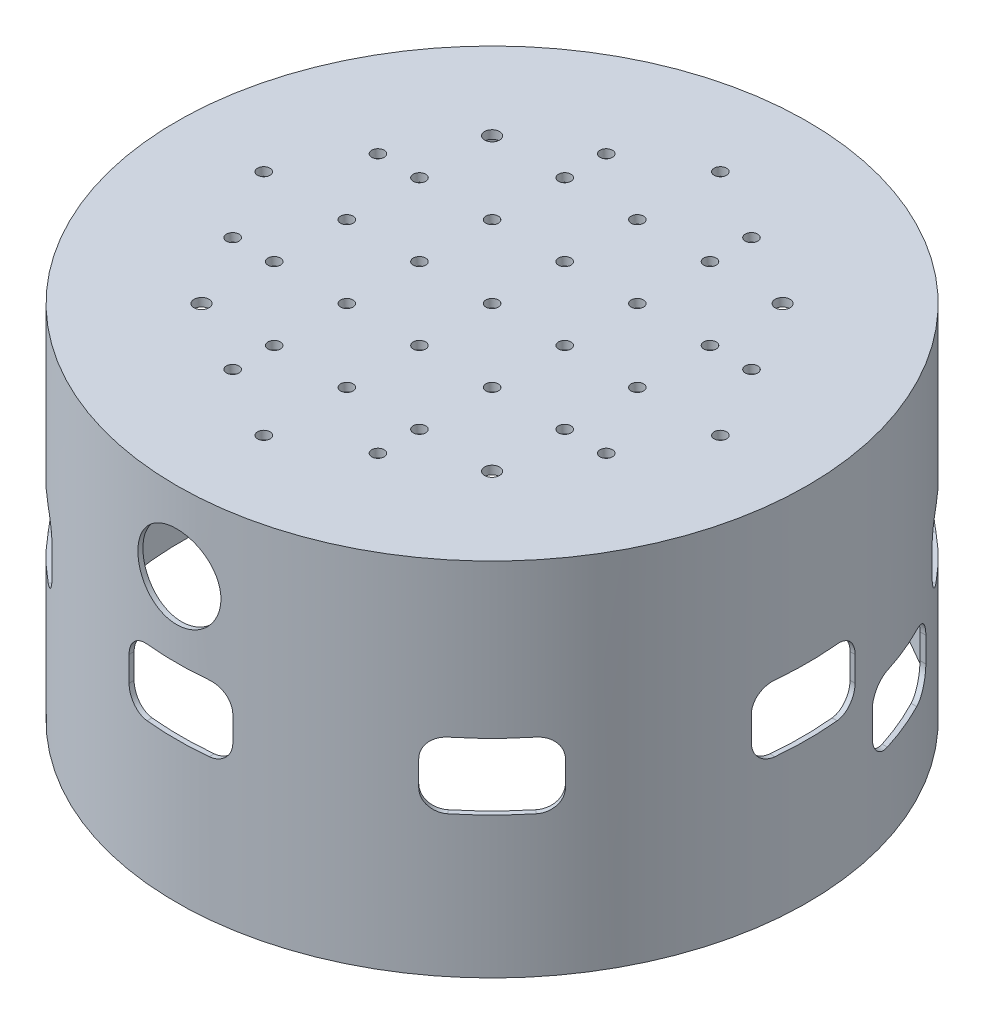
SolidWorks part; units mm, degrees
ref_plane "Front Plane" through (0, 0, 0) normal (0, 0, 1) x (1, 0, 0)
ref_plane "Top Plane" through (0, 0, 0) normal (0, 1, 0) x (1, 0, 0)
ref_plane "Right Plane" through (0, 0, 0) normal (1, 0, 0) x (0, 0, -1)
sketch "Sketch1" plane through (0, 0, 0) normal (0, 1, 0) x (1, 0, 0)
  circle A1 centre (0, 0) radius 76
extrude "Boss-Extrude1" add sketch "Sketch1" along normal blind 2
sketch "Sketch2" plane through (0, 0, 0) normal (0, -1, 0) x (1, 0, 0)
  circle A0 centre (0, 0) radius 76
  circle A1 centre (0, 0) radius 74
extrude "Boss-Extrude2" add sketch "Sketch2" along normal blind 85
ref_plane "Plane1" through (0, 0, 76) normal (0, 0, 1) x (1, 0, 0)
ref_plane "Plane2" through (-76, 0, 0) normal (-1, 0, 0) x (0, 0, 1)
sketch "Sketch4" plane through (0, 0, 76) normal (0, 0, 1) x (1, 0, 0)
  line L0 (0, 2) -> (0, -85) construction
  line L1 (76, 2) -> (-76, 2) construction
  line L2 (-76, -85) -> (76, -85) construction
  line L6 (0, 0) -> (0, -11) construction
  line L7 (83.6, 0) -> (-83.6, 0) construction
  line L8 (-10, -32) -> (10, -32) construction
  line L9 (-10, -32) -> (-10, -2) construction
  line L10 (-10, -2) -> (10, -2) construction
  line L11 (10, -32) -> (10, -2) construction
  line L12 (-10, -32) -> (10, -2) construction
  line L13 (-10, -2) -> (10, -32) construction
  circle A0 centre (0, -17) radius 10
  point P0 (0, -17)
  dimension "D1" = 2
  dimension "D3" = 30
  dimension "D2" = 20
extrude "Cut-Extrude1" cut sketch "Sketch4" against normal blind 10
sketch "Sketch5" plane through (0, 0, 76) normal (0, 0, 1) x (1, 0, 0)
  line L0 (0, -47.85) -> (0, 47.85) construction
  line L1 (-12.5, -51) -> (12.5, -51)
  line L2 (-12.5, -51) -> (-12.5, -35)
  line L3 (-12.5, -35) -> (12.5, -35)
  line L4 (12.5, -51) -> (12.5, -35)
  line L5 (-12.5, -51) -> (12.5, -35) construction
  line L6 (-12.5, -35) -> (12.5, -51) construction
  line L10 (0, -35) -> (0, 0) construction
  point P0 (0, -43)
  dimension "D1" = 35
extrude "Cut-Extrude2" cut sketch "Sketch5" against normal blind 10
fillet "Fillet1" radius 5 4 edges at (12.5, -51, 73.9508) (12.5, -35, 73.9508) (-12.5, -51, 73.9508) (-12.5, -35, 73.9508)
pattern_circular "CirPattern1" count 8 every 45 about axis through (0, 2, 0) along (0, 1, 0) of "Cut-Extrude2", "Fillet1"
sketch "Sketch6" plane through (0, 2, 0) normal (0, 1, 0) x (1, 0, 0)
  line L0 (-35, 0) -> (-75, 0) construction
  line L1 (-35, -35) -> (35, -35) construction
  line L2 (-35, -35) -> (-35, 35) construction
  line L3 (-35, 35) -> (35, 35) construction
  line L4 (35, -35) -> (35, 35) construction
  line L5 (-35, -35) -> (35, 35) construction
  line L6 (-35, 35) -> (35, -35) construction
  line L7 (0, 35) -> (0, 75) construction
  line L8 (35, 0) -> (75, 0) construction
  line L9 (0, -35) -> (0, -75) construction
  line L10 (-55, 0) -> (-55, 35) construction
  line L11 (-35, 35) -> (0, 0) construction
  line L12 (0, 0) -> (35, 35) construction
  line L13 (35, -35) -> (0, 0) construction
  line L14 (0, 55) -> (-35, 55) construction
  line L15 (-35, 55) -> (-35, 35) construction
  line L16 (-35, 35) -> (-55, 35) construction
  line L17 (-55, 35) -> (-35, 55) construction
  line L18 (-55, 0) -> (-35, 35) construction
  line L19 (-35, 35) -> (0, 55) construction
  line L20 (0, 35) -> (0, 0) construction
  line L21 (0, 0) -> (0, -35) construction
  line L22 (0, -35) -> (-35, 0) construction
  line L23 (-35, 0) -> (0, 0) construction
  line L24 (0, 0) -> (35, 0) construction
  circle A4 centre (0, 0) radius 1.5
  circle A5 centre (-35, 0) radius 1.5
  circle A6 centre (0, 35) radius 1.5
  circle A7 centre (35, 0) radius 1.5
  circle A8 centre (0, -35) radius 1.5
  circle A9 centre (-55, 0) radius 1.5
  circle A10 centre (0, 55) radius 1.5
  circle A11 centre (55, 0) radius 1.5
  circle A12 centre (0, -55) radius 1.5
  circle A13 centre (-17.5, 17.5) radius 1.5
  circle A14 centre (17.5, 17.5) radius 1.5
  circle A15 centre (-17.5, -17.5) radius 1.5
  circle A16 centre (17.5, -17.5) radius 1.5
  circle A19 centre (-45, 17.5) radius 1.5
  circle A20 centre (-17.5, 45) radius 1.5
  circle A21 centre (17.5, 45) radius 1.5
  circle A24 centre (45, 17.5) radius 1.5
  circle A25 centre (45, -17.5) radius 1.5
  circle A28 centre (17.5, -45) radius 1.5
  circle A29 centre (-17.5, -45) radius 1.5
  circle A32 centre (-45, -17.5) radius 1.5
  circle A33 centre (-35, 35) radius 1.8
  circle A34 centre (35, 35) radius 1.8
  circle A35 centre (-35, -35) radius 1.8
  circle A36 centre (0, 17.5) radius 1.5
  circle A37 centre (-17.5, 0) radius 1.5
  circle A38 centre (17.5, 0) radius 1.5
  circle A39 centre (0, -17.5) radius 1.5
  circle A40 centre (-17.5, -35) radius 1.5
  circle A41 centre (17.5, -35) radius 1.5
  circle A42 centre (35, -17.5) radius 1.5
  circle A43 centre (35, 17.5) radius 1.5
  circle A44 centre (17.5, 35) radius 1.5
  circle A45 centre (-17.5, 35) radius 1.5
  circle A46 centre (-35, 17.5) radius 1.5
  circle A47 centre (-35, -17.5) radius 1.5
  circle A48 centre (35, -35) radius 1.8
  point P0 (0, 0)
  point P78 (0, 0)
  dimension "D1" = 4
extrude "Cut-Extrude3" cut sketch "Sketch6" against normal blind 10
ref_plane "Plane3" through (0, 0, -76) normal (0, 0, -1) x (-1, 0, 0)
sketch "Sketch8" plane through (0, 0, -76) normal (0, 0, 1) x (1, 0, 0)
  line L0 (0, 0) -> (0, -53) construction
  line L1 (0, -47.85) -> (0, 47.85) construction
  line L4 (-25, -53) -> (25, -53)
  line L5 (-25, -53) -> (-25, -85)
  line L8 (-25, -85) -> (25, -85)
  line L9 (25, -53) -> (25, -85)
  line L10 (-76, -85) -> (76, -85) construction
  line L11 (7.5, -51) -> (-7.5, -51) construction
  point P8 (0, -53)
extrude "Cut-Extrude4" cut sketch "Sketch8" against normal mid plane 36
ref_plane "Plane4" through (0, -11, 0) normal (0, -1, 0) x (-1, 0, 0)
sketch "Sketch11" plane through (0, -85, 0) normal (0, -1, 0) x (-1, 0, 0)
  circle A0 centre (0, 0) radius 74
  circle A1 centre (0, 0) radius 74.8
  dimension "D1" = 0.8
extrude "Cut-Extrude7" cut sketch "Sketch11" against normal up to surface (85 mm away) up to face at (45, 0, -16)
fillet "Fillet5" radius 10 4 edges at (25, -85, -71.1345) (-25, -85, -71.1345) (-25, -53, -71.1345) (25, -53, -71.1345)
sketch "Sketch13" plane through (0, 0, 0) normal (1, 0, 0) x (0, 0, -1)
  line L0 (36.7, -57.6528) -> (20.7, -57.6528) construction
  line L1 (36.7, -60.6528) -> (36.7, -54.6528) construction
  line L2 (20.7, -54.6528) -> (20.7, -60.6528) construction
  line L4 (17.7, -65.6528) -> (39.7, -65.6528)
  line L5 (17.7, -65.6528) -> (17.7, -49.6528)
  line L6 (17.7, -49.6528) -> (39.7, -49.6528)
  line L7 (39.7, -65.6528) -> (39.7, -49.6528)
  line L8 (17.7, -65.6528) -> (39.7, -49.6528) construction
  line L9 (17.7, -49.6528) -> (39.7, -65.6528) construction
  point P6 (28.7, -57.6528)
extrude "Cut-Extrude9" cut sketch "Sketch13" against normal mid plane 179
fillet "Fillet6" radius 5 8 edges at (-73.2929, -65.6528, -17.7) (-64.101, -65.6528, -39.7) (-64.101, -49.6528, -39.7) (-73.2929, -49.6528, -17.7) (64.101, -65.6528, -39.7) (73.2929, -65.6528, -17.7) (73.2929, -49.6528, -17.7) (64.101, -49.6528, -39.7)
